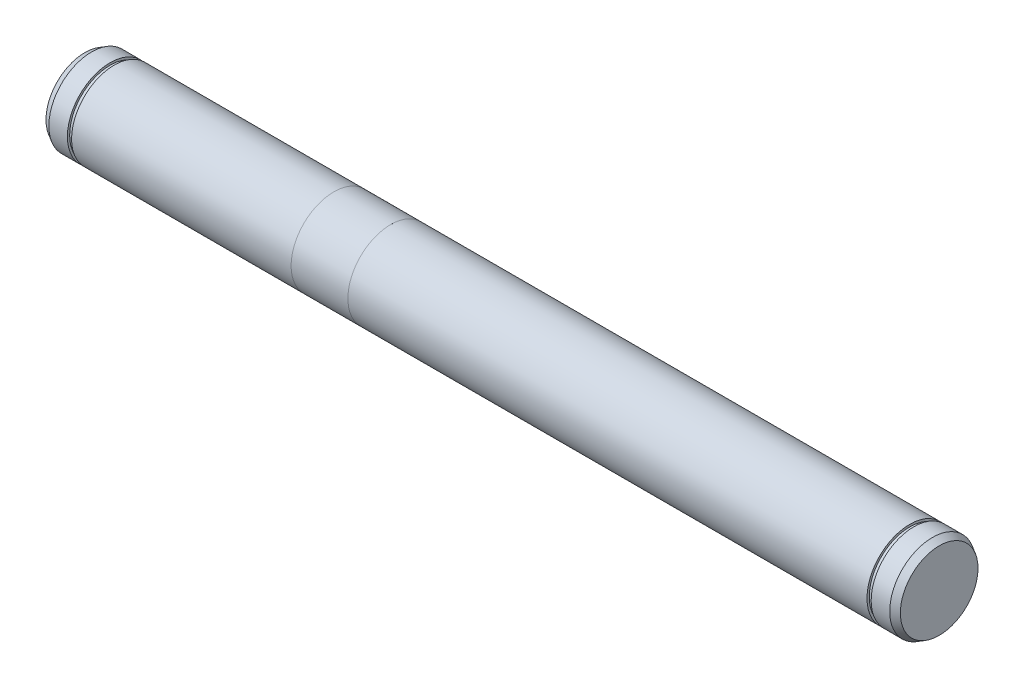
SolidWorks part; units mm, degrees
material "1.7225 (42CrMo4)"
ref_plane "E_Oben" through (0, 0, 0) normal (0, 0, 1) x (1, 0, 0)
ref_plane "E_Vorne" through (0, 0, 0) normal (0, 1, 0) x (1, 0, 0)
ref_plane "E_Rechts" through (0, 0, 0) normal (1, 0, 0) x (0, 0, -1)
ref_axis "A_Drehachse" through (-88.99, 0, 0) along (1, 0, 0)
sketch "Skizze1" plane through (0, 0, 0) normal (0, 0, 1) x (1, 0, 0)
  line L1 (0, -55) -> (0, 55) construction
  line L3 (190, 19) -> (190, 0)
  line L4 (190, 0) -> (-190, 0)
  line L5 (-54, 19.001) -> (-54, 19)
  line L6 (-54, 19.001) -> (-84, 19.001)
  line L7 (-190, 19) -> (-190, 0)
  line L10 (-89, 19) -> (-89, 27)
  line L11 (-89, 27) -> (-84, 27)
  line L12 (-84, 27) -> (-84, 19.001)
  line L14 (-190, 19) -> (-89, 19)
  line L17 (-54, 19) -> (190, 19)
  point P12 (0, 0)
  dimension "D1" = 101
  dimension "D2" = 19
  dimension "D3" = 19.001
  dimension "D4" = 190
  dimension "D5" = 27
  dimension "D6" = 30
  dimension "D7" = 5
revolve "Rotation1" add sketch "Skizze1" angle 360 about L4
sketch "Skizze19" plane through (0, 0, 0) normal (0, 0, 1) x (1, 0, 0)
  line L5 (-88.99, 0) -> (88.99, 0) construction
  line L8 (176.9, 19) -> (178.75, 19)
  line L9 (176.9, 19) -> (176.9, 18)
  line L10 (176.9, 18) -> (178.75, 18)
  line L11 (178.75, 19) -> (178.75, 18)
  line L14 (190, 19) -> (-54, 19) construction
  line L15 (190, -19) -> (190, 19) construction
  dimension "D1" = 11.25
  dimension "D2" = 0
  dimension "D4" = 1.85
  dimension "D5" = 18
revolve "Schnitt-Rotation1" cut sketch "Skizze19" angle 360 about axis through (-88.99, 0, 0) along (1, 0, 0)
sketch "Skizze20" plane through (0, 0, 0) normal (0, 0, 1) x (1, 0, 0)
  line L1 (-178.75, 19) -> (-176.9, 19)
  line L2 (-178.75, 19) -> (-178.75, 18)
  line L3 (-178.75, 18) -> (-176.9, 18)
  line L4 (-176.9, 19) -> (-176.9, 18)
  line L7 (-89, 19) -> (-190, 19) construction
  line L8 (-190, 19) -> (-190, -19) construction
  dimension "D1" = 11.25
  dimension "D2" = 1.85
  dimension "D3" = 1
  dimension "D4" = 0
revolve "Schnitt-Rotation2" cut sketch "Skizze20" angle 360 about axis through (-88.99, 0, 0) along (1, 0, 0)
sketch "Sketch1" plane through (0, 0, 0) normal (0, 0, 1) x (1, 0, 0)
  line L0 (-89, 19) -> (-176.9, 19) construction
  line L1 (-93.331, 19) -> (-79.2296, 19)
  line L2 (-93.331, 19) -> (-93.331, 30.2934)
  line L3 (-93.331, 30.2934) -> (-79.2296, 30.2934)
  line L4 (-79.2296, 19) -> (-79.2296, 30.2934)
  line L5 (-190, 19) -> (-190, -19) construction
  line L6 (-191.1647, 0) -> (203.9937, 0) construction
  dimension "D1" = 14.1014
  dimension "D2" = 11.2934
  dimension "D3" = 110.7704
revolve "Cut-Revolve1" cut sketch "Sketch1" angle 360 about L6
chamfer "倒角1" distance 3 angle 30 2 edges at (190, 0, -19) (-190, 0, -19) first distance on face at (190, 0, -19) first distance on face at (-190, 0, -19)
